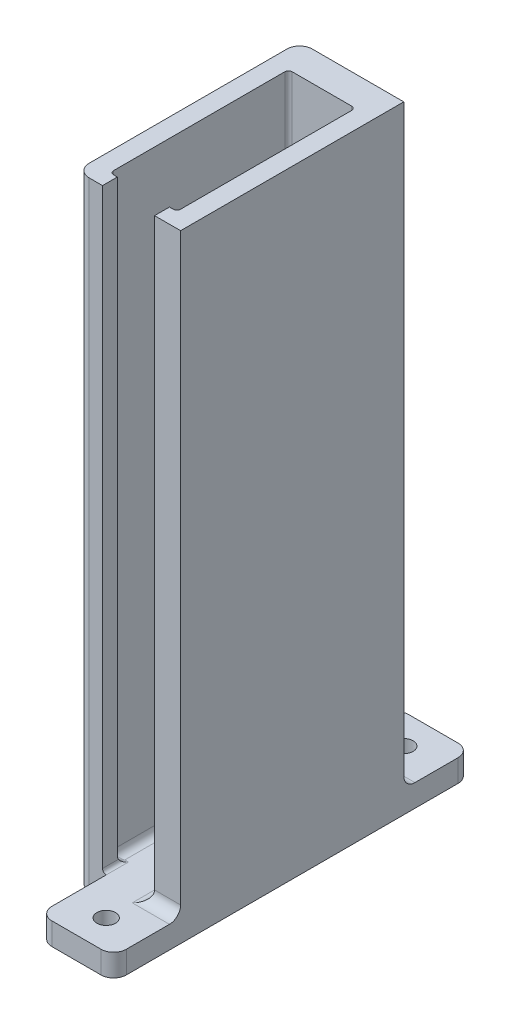
SolidWorks part; units mm, degrees
material "PLA2"
ref_plane "Front Plane" through (0, 0, 0) normal (0, 0, 1) x (1, 0, 0)
ref_plane "Top Plane" through (0, 0, 0) normal (0, 1, 0) x (1, 0, 0)
ref_plane "Right Plane" through (0, 0, 0) normal (1, 0, 0) x (0, 0, -1)
sketch "Sketch1" plane through (0, 0, 0) normal (1, 0, 0) x (0, 0, -1)
  line L0 (0, 0) -> (0, 3.81)
  line L1 (0, 3.81) -> (11.43, 3.81)
  line L2 (11.43, 3.81) -> (11.43, 105.41)
  line L3 (11.43, 105.41) -> (49.53, 105.41)
  line L4 (49.53, 105.41) -> (49.53, 3.81)
  line L5 (49.53, 3.81) -> (60.96, 3.81)
  line L6 (60.96, 3.81) -> (60.96, 0)
  line L7 (60.96, 0) -> (0, 0)
  dimension "D1" = 11.43
  dimension "D2" = 38.1
  dimension "D3" = 3.81
  dimension "D4" = 101.6
extrude "Boss-Extrude1" add sketch "Sketch1" along normal blind 17.78
sketch "Sketch4" plane through (0, 3.81, 0) normal (0, 1, 0) x (1, 0, 0)
  line L0 (5.08, 60.96) -> (5.08, 49.53)
  line L1 (17.78, 60.96) -> (0, 60.96) construction
  line L2 (17.78, 49.53) -> (0, 49.53) construction
  line L3 (5.08, 49.53) -> (0, 49.53)
  line L4 (0, 49.53) -> (0, 60.96)
  line L5 (0, 60.96) -> (5.08, 60.96)
  line L6 (17.78, 60.96) -> (17.78, 49.53) construction
  line L7 (0, 30.48) -> (17.78, 30.48) construction
  line L8 (0, 49.53) -> (0, 11.43) construction
  line L9 (17.78, 49.53) -> (17.78, 11.43) construction
  line L10 (0, 0) -> (5.08, 0)
  line L11 (0, 11.43) -> (0, 0)
  line L12 (5.08, 11.43) -> (0, 11.43)
  line L13 (5.08, 0) -> (5.08, 11.43)
  dimension "D1" = 12.7
extrude "Cut-Extrude2" cut sketch "Sketch4" against normal through all
sketch "Sketch2" plane through (0, 105.41, 0) normal (0, 1, 0) x (1, 0, 0)
  line L0 (8.89, 49.53) -> (8.89, 11.43) construction
  line L1 (17.78, 49.53) -> (0, 49.53) construction
  line L2 (17.78, 11.43) -> (5.08, 11.43) construction
  line L3 (14.605, 44.45) -> (3.175, 44.45)
  line L4 (3.175, 44.45) -> (3.175, 13.97)
  line L5 (3.175, 13.97) -> (4.445, 13.97)
  line L6 (4.445, 13.97) -> (4.445, 11.43)
  line L7 (4.445, 11.43) -> (13.335, 11.43)
  line L8 (13.335, 13.97) -> (13.335, 11.43)
  line L9 (14.605, 13.97) -> (13.335, 13.97)
  line L10 (14.605, 44.45) -> (14.605, 13.97)
  point P15 (8.89, 44.45)
  dimension "D1" = 11.43
  dimension "D2" = 30.48
  dimension "D3" = 2.54
  dimension "D4" = 8.89
extrude "Cut-Extrude1" cut sketch "Sketch2" against normal blind 101.6
sketch "Sketch3" plane through (0, 3.81, 0) normal (0, 1, 0) x (1, 0, 0)
  line L0 (5.08, 30.48) -> (17.78, 30.48) construction
  line L2 (17.78, 49.53) -> (17.78, 11.43) construction
  line L3 (11.43, 5.08) -> (11.43, 55.88) construction
  line L4 (5.08, 51.6451) -> (5.08, 30.48) construction
  line L5 (5.08, 49.53) -> (5.08, 60.96) construction
  circle A0 centre (11.43, 55.88) radius 1.5875
  circle A1 centre (11.43, 5.08) radius 1.5875
  point P10 (11.43, 30.48)
  dimension "D1" = 3.175
  dimension "2" = 50.8
extrude "Bottom_Mount_Holes" cut sketch "Sketch3" against normal blind 101.6
fillet "Fillet1" radius 1.905 4 edges at (11.43, 3.81, -49.53) (13.335, 3.81, -12.7) (15.5575, 3.81, -11.43) (5.08, 1.905, -49.53)
fillet "Fillet2" radius 1.27 5 edges at (13.0175, 3.81, -13.97) (3.81, 3.81, -13.97) (14.605, 3.81, -29.21) (8.89, 3.81, -44.45) (3.175, 3.81, -29.21)
fillet "Fillet3" radius 0.635 8 edges at (14.233, 4.182, -14.342) (3.547, 4.182, -14.342) (14.233, 4.182, -44.078) (3.547, 4.182, -44.078) (14.605, 55.245, -13.97) (3.175, 55.245, -13.97) (14.605, 55.245, -44.45) (3.175, 55.245, -44.45)
fillet "Fillet4" radius 2.159 6 edges at (17.78, 1.905, 0) (5.08, 1.905, 0) (0, 52.705, -11.43) (0, 52.705, -49.53) (17.78, 1.905, -60.96) (5.08, 1.905, -60.96)
fillet "Fillet5" radius 0.635 2 edges at (4.7625, 3.81, -11.43) (4.445, 3.81, -13.335)
